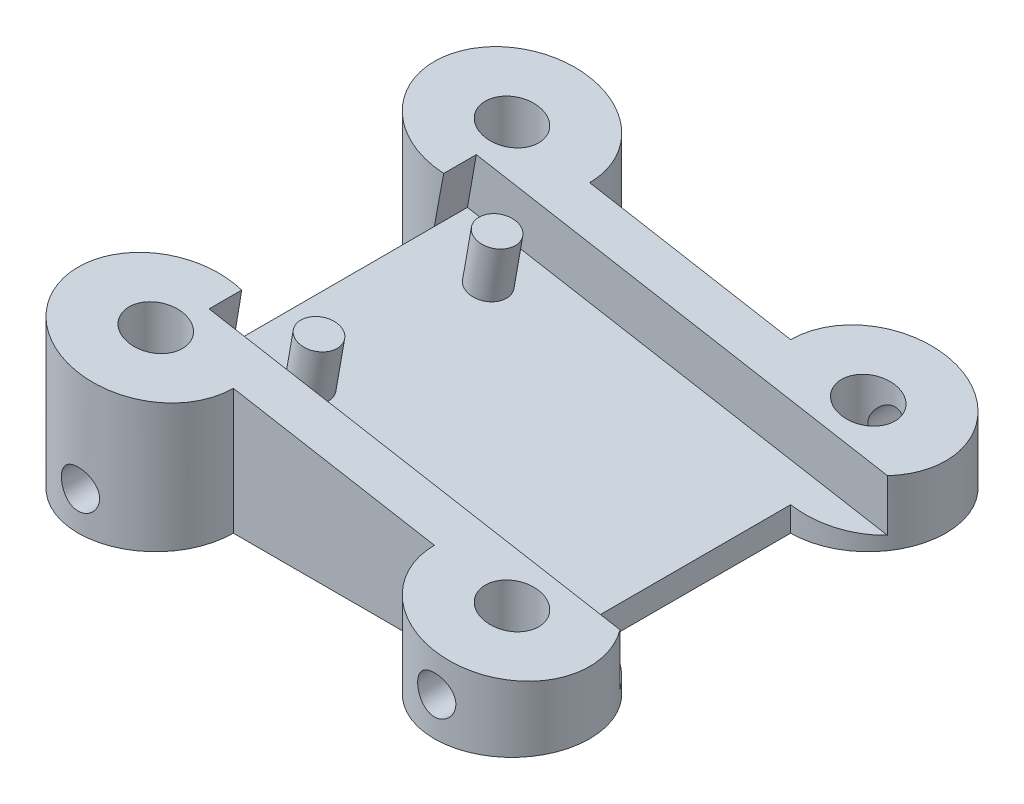
SolidWorks part; units mm, degrees
ref_plane "Front Plane" through (0, 0, 0) normal (0, 0, 1) x (1, 0, 0)
ref_plane "Top Plane" through (0, 0, 0) normal (0, 1, 0) x (1, 0, 0)
ref_plane "Right Plane" through (0, 0, 0) normal (1, 0, 0) x (0, 0, -1)
sketch "Sketch1" plane through (0, 0, 0) normal (0, 1, 0) x (1, 0, 0)
  line L0 (14, 28) -> (14, 0) construction
  line L1 (0, 0) -> (28, 0)
  line L2 (0, 0) -> (0, 28)
  line L3 (0, 28) -> (28, 28)
  line L4 (28, 0) -> (28, 28)
  line L5 (0, 14) -> (28, 14) construction
  point P9 (14, 14)
  dimension "D1" = 28
extrude "Boss-Extrude1" add sketch "Sketch1" along normal blind 10.9372
sketch "Sketch2" plane through (0, 0, 0) normal (0, 0, 1) x (1, 0, 0)
  line L0 (0, 10.9372) -> (28, 6)
  line L1 (0, 10.9372) -> (28, 10.9372) construction
  line L2 (28, 10.9372) -> (28, 0) construction
  line L3 (0, 10.9372) -> (28, 10.9372)
  line L4 (28, 10.9372) -> (28, 6)
  dimension "D2" = 6
  dimension "D3" = 10
extrude "Cut-Extrude1" cut sketch "Sketch2" against normal through all
sketch "Sketch3" plane through (1.8704, 10.6074, 0) normal (0.1736, 0.9848, 0) x (0.9848, -0.1736, 0)
  line L0 (-1.8992, 28) -> (-1.8992, 0) construction
  line L1 (-1.8992, 3.5) -> (48.1008, 3.5)
  line L2 (-1.8992, 3.5) -> (-1.8992, 24.5)
  line L3 (-1.8992, 24.5) -> (48.1008, 24.5)
  line L4 (48.1008, 3.5) -> (48.1008, 24.5)
  point P9 (-1.8992, 14)
  point P10 (-1.8992, 14)
  dimension "D1" = 21
  dimension "D2" = 50
extrude "Cut-Extrude2" cut sketch "Sketch3" against normal blind 4
ref_plane "Plane1" through (0, 10.9372, 0) normal (0, 1, 0) x (1, 0, 0)
sketch "Sketch11" plane through (1.1758, 6.6681, 0) normal (0.1736, 0.9848, 0) x (0.9848, -0.1736, 0)
  line L0 (27.238, 24.5) -> (-1.1939, 24.5) construction
  line L1 (27.238, 24.5) -> (27.238, 3.5) construction
  line L2 (-1.1939, 3.5) -> (27.238, 3.5) construction
  line L3 (27.238, 24.5) -> (-1.1939, 24.5) construction
  line L4 (27.238, 24.5) -> (27.238, 3.5) construction
  line L5 (-1.1939, 3.5) -> (27.238, 3.5) construction
  line L6 (13.0221, 3) -> (13.0221, 50003) construction
  line L7 (24.633, 14) -> (-49975.367, 14) construction
  circle A2 centre (4.0221, 21) radius 1.45
  circle A3 centre (4.0221, 7) radius 1.45
  point P6 (13.0221, 3.5)
  point P9 (27.238, 14)
  dimension "D4" = 2.9
  dimension "D5" = 9
  dimension "D6" = 7
extrude "Boss-Extrude2" add sketch "Sketch11" along normal blind 4
sketch "Sketch12" plane through (0, 10.9372, 0) normal (0, 1, 0) x (1, 0, 0)
  line L0 (0, 3.5) -> (0, 24.5) construction
  line L1 (0, 3.5) -> (28, 3.5) construction
  line L2 (0, 3.5) -> (0, 24.5) construction
  line L3 (0, 3.5) -> (28, 3.5) construction
  line L4 (0, 14) -> (50000, 14) construction
  line L5 (14, 4) -> (14, 50004) construction
  circle A0 centre (14, 14) radius 7
  point P7 (0, 14)
  point P10 (14, 3.5)
  dimension "D1" = 14
sketch "Sketch13" plane through (0, 0, 0) normal (0, -1, 0) x (1, 0, 0)
  line L0 (0, 0) -> (28, 0) construction
  line L1 (28, 0) -> (28, -28) construction
  line L2 (28, -28) -> (0, -28) construction
  line L3 (0, -28) -> (0, 0) construction
  line L4 (0, 0) -> (28, 0) construction
  line L5 (28, 0) -> (28, -28) construction
  line L6 (28, -28) -> (0, -28) construction
  line L7 (0, -28) -> (0, 0) construction
  line L8 (0, -14) -> (28, -14) construction
  line L9 (14, -28) -> (14, 0) construction
  circle A0 centre (0, 0) radius 2.1
  circle A1 centre (28, 0) radius 2.1
  circle A2 centre (28, -28) radius 2.1
  circle A3 centre (0, -28) radius 2.1
  dimension "D1" = 4.2
  dimension "D2" = 2
  dimension "D3" = 2
extrude "Cut-Extrude5" cut sketch "Sketch13" against normal through all
sketch "Sketch14" plane through (0, 0, 0) normal (0, -1, 0) x (1, 0, 0)
  line L0 (28, -3.5) -> (28, -2.1) construction
  line L1 (2.1, -28) -> (25.9, -28) construction
  line L2 (0, -3.5) -> (0, -24.5) construction
  circle A0 centre (0, 0) radius 2.1 construction
  circle A1 centre (0, 0) radius 2.1 construction
  circle A2 centre (0, 0) radius 6.1
  circle A3 centre (0, 0) radius 2.1
  circle A4 centre (28, 0) radius 2.1
  circle A5 centre (28, 0) radius 6.1
  circle A6 centre (28, -28) radius 2.1
  circle A7 centre (28, -28) radius 6.1
  circle A8 centre (0, -28) radius 2.1
  circle A9 centre (0, -28) radius 6.1
  dimension "D1" = 4
  dimension "D4" = 4.2
  dimension "D2" = 2
  dimension "D3" = 2
extrude "Boss-Extrude3" add sketch "Sketch14" against normal up to surface (10.9372 mm away) up to face at (14, 8.4686, -25.9884)
sketch "Sketch15" plane through (0, 0, -28) normal (0, 0, -1) x (-1, 0, 0)
  line L0 (-21.9, 0) -> (-6.1, 0) construction
  line L1 (-21.9, 0) -> (-0.9, 0) construction
  line L4 (-14, 8.4686) -> (-14, 0) construction
  line L5 (-6.1, 9.8616) -> (-21.9, 7.0756) construction
  circle A0 centre (-28, 3) radius 1.5
  circle A1 centre (0, 3) radius 1.5
  point P4 (-28, 0)
  dimension "D1" = 3
  dimension "D2" = 3
extrude "Cut-Extrude6" cut sketch "Sketch15" along normal through all
sketch "Sketch16" plane through (0, 0, 0) normal (0, 0, 1) x (1, 0, 0)
  circle A0 centre (0, 3) radius 1.5 construction
  circle A1 centre (28, 3) radius 1.5 construction
  circle A2 centre (0, 3) radius 1.5
  circle A3 centre (28, 3) radius 1.5
extrude "Cut-Extrude7" cut sketch "Sketch16" along normal through all
sketch "Sketch18" plane through (1.8704, 10.6074, 0) normal (0.1736, 0.9848, 0) x (0.9848, -0.1736, 0)
  line L5 (-1.8992, 3.5) -> (25.6754, 3.5) construction
  line L8 (3.1739, 3.5) -> (21.4597, 3.5) construction
  line L9 (3.1739, 3.5) -> (21.4597, 3.5) construction
  line L22 (3.8792, 24.5) -> (-1.1939, 24.5)
  line L37 (6.4597, 3.5) -> (36.4597, 3.5)
  line L38 (6.4597, 3.5) -> (6.4597, 24.5)
  line L39 (6.4597, 24.5) -> (36.4597, 24.5)
  line L40 (36.4597, 3.5) -> (36.4597, 24.5)
  line L42 (-1.1939, 24.5) -> (-1.1939, 21.9)
  line L46 (-1.1939, 6.1) -> (-1.1939, 3.5)
  line L47 (-1.1939, 3.5) -> (3.8792, 3.5)
  line L49 (3.1739, 24.5) -> (21.4597, 24.5) construction
  ellipse E1 centre (-1.1939, 28) end of major axis (5.0002, 28) minor radius 6.1 (-1.1939, 21.9) -> (3.8792, 24.5) ccw construction
  ellipse E2 centre (-1.1939, 28) end of major axis (5.0002, 28) minor radius 6.1 (-1.1939, 21.9) -> (3.8792, 24.5) ccw
  ellipse E3 centre (-1.1939, 0) end of major axis (5.0002, 0) minor radius 6.1 (3.8792, 3.5) -> (-1.1939, 6.1) ccw construction
  ellipse E4 centre (-1.1939, 0) end of major axis (5.0002, 0) minor radius 6.1 (3.8792, 3.5) -> (-1.1939, 6.1) ccw
  point P7 (21.4597, 3.5)
  dimension "D1" = 30
extrude "Cut-Extrude8" cut sketch "Sketch18" against normal up to surface (4 mm away) up to face at (6.5647, 5.7179, -21)
equation "\"TrackLength\"= 150"
equation "\"MarbleWidth\"= 13"
equation "\"MarbleTrackWidth\"= \"MarbleWidth\" - 1"
equation "\"TrackWidth\"= \"MarbleTrackWidth\" + ( 2 * 4 )"
equation "\"MarbleTrackLength\"= \"TrackLength\" - ( 2 * 8 )"
equation "\"MountWidth\"= \"TrackWidth\" + 8"
equation "\"D1@Sketch1\"=\"MountWidth\""
equation "\"D1@Boss-Extrude1\"=\"RampHeight\""
equation "\"RampDepth\"=6"
equation "\"RampAngle\"= 10"
equation "\"RampHeight\"= ( \"MountWidth\" * tan ( \"RampAngle\" ) ) + \"RampDepth\""
equation "\"D1@Sketch3\"=\"TrackWidth\" + 1"
equation "\"MountWidth\"= \"TrackWidth\" + 10"
equation "\"MountLength\"=66.6651"
